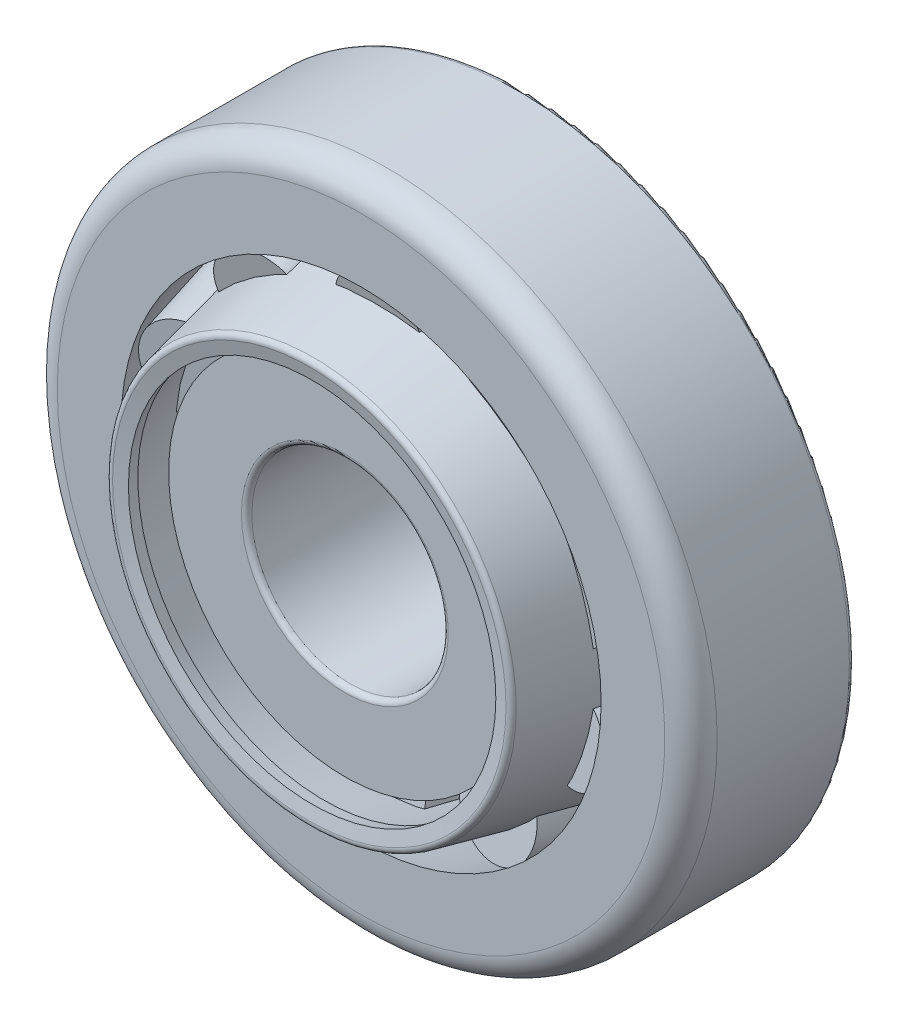
SolidWorks part; units mm, degrees
ref_plane "Front Plane" through (0, 0, 0) normal (0, 0, 1) x (1, 0, 0)
ref_plane "Top Plane" through (0, 0, 0) normal (0, 1, 0) x (1, 0, 0)
ref_plane "Right Plane" through (0, 0, 0) normal (1, 0, 0) x (0, 0, -1)
sketch "Sketch1" plane through (0, 0, 0) normal (1, 0, 0) x (0, 0, -1)
  line L0 (-3.9688, 16.002) -> (-3.9688, 11.645)
  line L1 (-3.9688, 11.645) -> (3.9688, 13.79)
  line L2 (3.9688, 13.79) -> (3.9688, 16.002)
  line L3 (3.9688, 16.002) -> (-3.9688, 16.002)
  line L4 (0, 0) -> (10110.1541, 0) construction
  line L5 (-0.4155, 12.6052) -> (2.9909, 0) construction
  line L6 (6.0388, 9.975) -> (6.0389, 4.7625)
  line L7 (6.0389, 4.7625) -> (-4.7561, 4.7625)
  line L8 (-4.7561, 4.7625) -> (-4.7561, 8.545)
  line L9 (-4.7561, 8.545) -> (-2.7626, 8.545)
  line L10 (6.0388, 9.975) -> (4.2848, 9.975)
  line L12 (6.0388, 16.002) -> (-6.5342, 16.002) construction
  line L14 (-6.5341, 9.7893) -> (5.1479, 12.3609)
  line L15 (5.1479, 12.3609) -> (5.2768, 11.7749)
  line L16 (5.2768, 11.7749) -> (-5.8192, 9.3323)
  line L17 (-5.8192, 9.3323) -> (-5.7547, 9.0393)
  line L18 (-3.4744, 11.7786) -> (3.4744, 13.6564) construction
  line L19 (-6.5341, 9.7893) -> (-6.3407, 8.9103)
  line L20 (-6.3407, 8.9103) -> (-5.7547, 9.0393)
  line L21 (3.4744, 13.6564) -> (4.5386, 8.8222)
  line L22 (4.5386, 8.8222) -> (-2.5564, 7.6084)
  line L23 (-2.5564, 7.6084) -> (-3.4744, 11.7786)
  line L25 (-3.0154, 9.6935) -> (4.0065, 11.2393) construction
  line L27 (0, 12.7175) -> (0.4955, 10.4664) construction
  line L28 (0.4955, 10.4664) -> (0.9911, 8.2153) construction
  line L29 (-6.5342, 16.002) -> (-6.5341, 9.7893) construction
  point P7 (0, 16.002)
  point P44 (3.9527, 11.4834)
  dimension "Width" = 7.9375
  dimension "Inner Ring Width" = 10.795
  dimension "D17" = 0.3
  dimension "D2" = 0.25
  dimension "D3" = 12.573
  dimension "ID" = 9.525
  dimension "OD" = 32.004
  dimension "Cage Width" = 12.573
sketch "Sketch0" plane through (0, 0, 0) normal (0, 0, 1) x (1, 0, 0)
  circle A0 centre (0, 0) radius 4.7625
  circle A1 centre (0, 0) radius 16.002
  dimension "D1" = 32.004
  dimension "D2" = 9.525
sketch "Sketch2" plane through (0, 0, 0) normal (1, 0, 0) x (0, 0, -1)
  line L0 (-3.9688, 16.002) -> (-3.9688, 11.645)
  line L1 (-3.9688, 11.645) -> (3.9688, 13.79)
  line L2 (3.9688, 13.79) -> (3.9688, 16.002)
  line L3 (3.9688, 16.002) -> (-3.9688, 16.002)
revolve "Revolve1" add sketch "Sketch2" angle 360 about L4
sketch "Sketch3" plane through (0, 0, 0) normal (1, 0, 0) x (0, 0, -1)
  line L0 (-4.7561, 8.545) -> (-4.7561, 4.7625)
  line L1 (-4.7561, 4.7625) -> (6.0389, 4.7625)
  line L2 (6.0389, 4.7625) -> (6.0388, 9.975)
  line L3 (6.0388, 9.975) -> (4.2848, 9.975)
  line L4 (4.2848, 9.975) -> (4.5386, 8.8222)
  line L5 (4.5386, 8.8222) -> (-2.5564, 7.6084)
  line L6 (-2.5564, 7.6084) -> (-2.7626, 8.545)
  line L7 (-2.7626, 8.545) -> (-4.7561, 8.545)
revolve "Revolve2" add sketch "Sketch3" angle 360 about L4
sketch "Sketch4" plane through (0, 0, 0) normal (1, 0, 0) x (0, 0, -1)
  line L0 (5.2768, 11.7749) -> (5.1479, 12.3609)
  line L1 (5.1479, 12.3609) -> (-6.5341, 9.7893)
  line L2 (-6.5341, 9.7893) -> (-6.3407, 8.9103)
  line L3 (-6.3407, 8.9103) -> (-5.7547, 9.0393)
  line L4 (-5.7547, 9.0393) -> (-5.8192, 9.3323)
  line L5 (-5.8192, 9.3323) -> (5.2768, 11.7749)
revolve "Revolve3" add sketch "Sketch4" angle 360 about L4
sketch "Sketch6" plane through (0, 0, 0) normal (1, 0, 0) x (0, 0, -1)
  line L0 (4.5386, 8.8222) -> (4.0065, 11.2393)
  line L1 (4.0065, 11.2393) -> (-3.0154, 9.6935)
  line L3 (-3.0154, 9.6935) -> (-2.5564, 7.6084)
  line L4 (-2.5564, 7.6084) -> (4.5386, 8.8222)
  line L5 (-3.0154, 9.6935) -> (4.0065, 11.2393) construction
  line L6 (-2.5564, 7.6084) -> (-3.4744, 11.7786) construction
revolve "Revolve4" add sketch "Sketch6" angle 360 about L25
pattern_circular "CirPattern1" count 10 over 360 about axis through (0, 0, 0) along (0, 0, -1) of "Revolve4"
fillet "Fillet1" radius 1.27 1 edges at (4.7625, 0, -6.0389)
fillet "Fillet2" radius 1.27 1 edges at (16.002, 0, 3.9688)
fillet "Fillet3" radius 0.254 1 edges at (4.7625, 0, 4.7561)
fillet "Fillet4" radius 0.254 1 edges at (16.002, 0, -3.9688)
fillet "Fillet5" radius 0.254 1 edges at (9.7893, 0, 6.5341)
sketch "Sketch7" plane through (0, 0, 0) normal (1, 0, 0) x (0, 0, -1)
  line L0 (6.0388, 9.975) -> (6.0389, 4.7625) construction
  line L1 (-4.7561, 8.545) -> (-2.7626, 8.545) construction
  line L2 (-4.7561, 4.7625) -> (-4.7561, 8.545) construction
  line L3 (6.0389, 4.7625) -> (-4.7561, 4.7625) construction
  line L4 (6.0388, 9.975) -> (4.2848, 9.975) construction
  line L5 (4.5386, 8.8222) -> (-2.5564, 7.6084) construction
  line L6 (3.4744, 13.6564) -> (4.5386, 8.8222) construction
  line L7 (-3.9688, 11.645) -> (3.9688, 13.79) construction
  line L8 (-2.5564, 7.6084) -> (-3.4744, 11.7786) construction
  line L9 (6.0388, 9.975) -> (6.0389, 4.7625)
  line L10 (-4.7561, 8.545) -> (-2.7626, 8.545)
  line L11 (-4.7561, 4.7625) -> (-4.7561, 8.545)
  line L12 (6.0389, 4.7625) -> (-4.7561, 4.7625)
  line L13 (6.0388, 9.975) -> (4.2848, 9.975)
  line L14 (4.5386, 8.8222) -> (-2.5564, 7.6084)
  line L15 (3.4744, 13.6564) -> (4.5386, 8.8222)
  line L16 (-3.4744, 11.7786) -> (3.4744, 13.6564)
  line L17 (-2.5564, 7.6084) -> (-3.4744, 11.7786)
  line L18 (0, 0) -> (-6.2861, 0) construction
  line L19 (-200000, 0) -> (210110.1541, 0) construction
  line L20 (-6.2861, -9.8439) -> (-6.2861, 9.8439) construction
  line L21 (-2.5564, -7.6084) -> (-3.4744, -11.7786)
  line L22 (-3.4744, -11.7786) -> (3.4744, -13.6564)
  line L23 (3.4744, -13.6564) -> (4.5386, -8.8222)
  line L24 (4.5386, -8.8222) -> (-2.5564, -7.6084)
  line L25 (6.0389, -9.975) -> (4.2848, -9.975)
  line L26 (6.0389, -4.7625) -> (-4.7561, -4.7625)
  line L27 (-4.7561, -4.7625) -> (-4.7561, -8.545)
  line L28 (-4.7561, -8.545) -> (-2.7626, -8.545)
  line L29 (6.0389, -9.975) -> (6.0389, -4.7625)
move or copy body "Body-Move/Copy1" [suppressed] bodies to move or copy 104 copy no translate (0, 0, 33.3375)
ref_plane "Contact Plane 1" through (0, 0, 3.9688) normal (0, 0, 1) x (1, 0, 0)
ref_plane "Contact Plane 2" through (0, 0, -3.9688) normal (0, 0, -1) x (-1, 0, 0)
ref_axis "Center Axis 1" through (0, 0, -4.7688) along (0, 0, 1)
ref_axis "Axis1" through (0, 0, -4.7688) along (0, 0, 1)
ref_plane "Plane1" through (0, 0, 6.4795) normal (0, 0, 1) x (1, 0, 0)
equation "\"D17@Sketch1\" = \"Cone Thick@Sketch1\" / 2"
equation "\"D1@Fillet4\"=\"D1@Fillet3\""
equation "\"D1@Fillet5\"=\"D1@Fillet4\""
